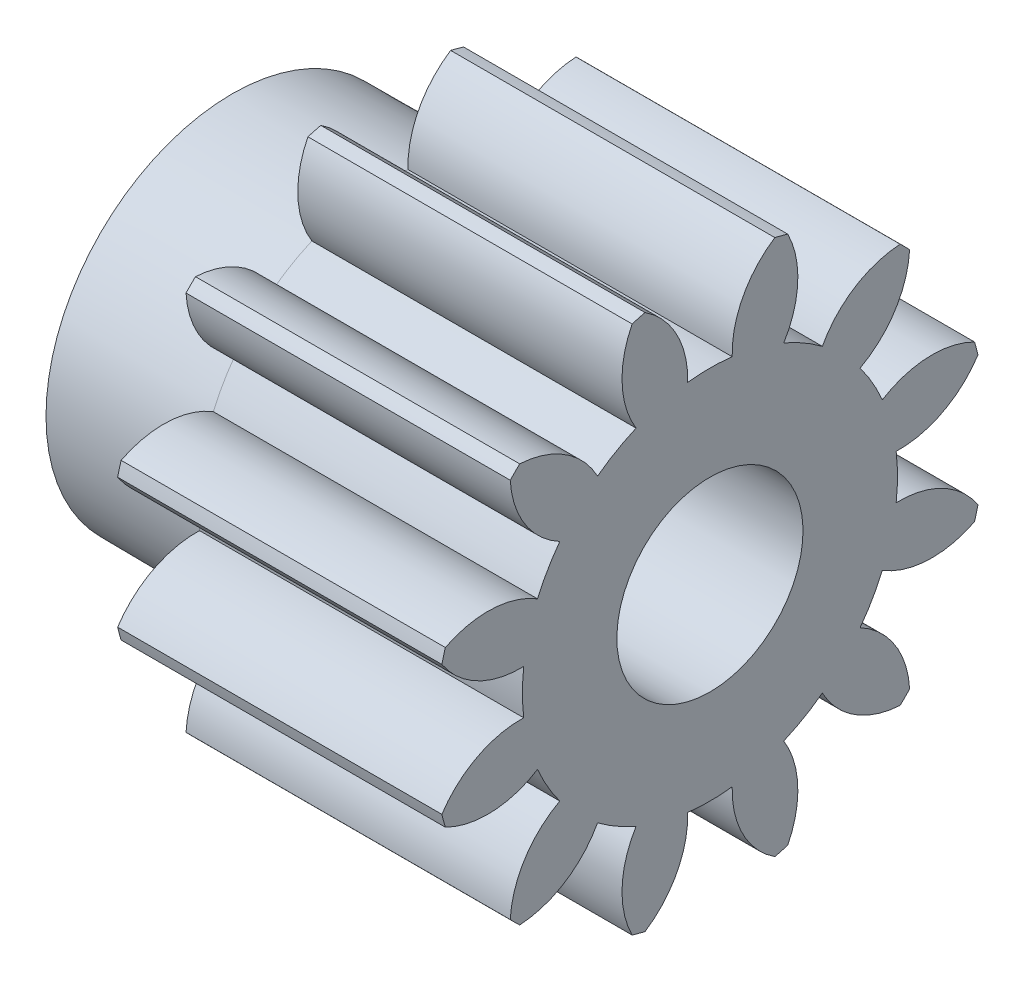
SolidWorks part; units mm, degrees
ref_plane "Plane1" through (0, 0, 0) normal (0, 0, 1) x (1, 0, 0)
ref_plane "Plane2" through (0, 0, 0) normal (0, 1, 0) x (1, 0, 0)
ref_plane "Plane3" through (0, 0, 0) normal (1, 0, 0) x (0, 0, -1)
sketch "HoldingSke" plane through (0, 0, 0) normal (0, 1, 0) x (1, 0, 0)
  line L0 (0, 0) -> (496.899, -105.6191)
  line L1 (-15, 0) -> (100, 0) construction
  line L2 (0, 0) -> (-2.1039, 2.3779)
  line L3 (0, 0) -> (-11.863, 4.5341)
  line L4 (0, 0) -> (8.4473, 1.7955)
  line L5 (0, 0) -> (-47.5972, -17.7524)
  line L6 (0, 0) -> (-10.5278, -7.1032)
  line L7 (-2.1039, 2.3779) -> (8.8308, 51.9871)
  line L8 (-76.2, 54.61) -> (-69.596, 54.61)
  line L9 (-71.009, 38.7566) -> (-53.1078, 45.2721)
  line L10 (-76.2, 71.12) -> (104.1128, 71.12)
  line L11 (0, 0) -> (-12.7, 0)
  line L12 (-76.2, 101.6) -> (-76.1492, 101.6)
  line L13 (24.9733, 27.94) -> (52.9518, 28.4284)
  line L14 (24.9733, 27.94) -> (25.0241, 27.9398)
  line L15 (24.9733, 27.94) -> (100.4021, 29.52)
  circle A0 centre (0, 0) radius 3.175
  circle A1 centre (0, 0) radius 6.0452
  circle A2 centre (0, 0) radius 38.1
  circle A3 centre (0, 0) radius 3.175
  dimension "Num_teeth" = 12
  dimension "H" = 19.05
  dimension "Pitch_radius" = 180.3128
  dimension "Width" = 12.7
  dimension "Thickness" = 12.7
sketch "BasProSke" plane through (0, 0, 0) normal (0, 1, 0) x (1, 0, 0)
  line L0 (-10, 0) -> (60, 0) construction
  line L1 (0, 0) -> (0, 8.89)
  line L2 (0, 0) -> (12.7, 0)
  line L3 (12.7, 0) -> (12.7, 8.89)
  line L4 (12.7, 8.89) -> (0, 8.89)
  dimension "Thickness" = 12.7
  dimension "Diameter" = 17.78
revolve "Base-Revolve" add sketch "BasProSke" angle 360 about L0
sketch "TooCutSke" plane through (0, 0, 0) normal (1, 0, 0) x (0, 0, -1)
  line L1 (0, 0) -> (0, 107) construction
  line L2 (0, 0) -> (-1.0834, 7.5426) construction
  line L3 (0, 0) -> (-3.9164, 14.6164) construction
  line L4 (-1.0834, 7.5426) -> (-1.9582, 7.3082) construction
  arc A0 (0.7171, 6.0025) -> (-0.7171, 6.0025) centre (0, 0) ccw
  arc A1 (2.1216, 8.6593) -> (-2.1216, 8.6593) centre (0, 0) ccw
  circle A2 centre (0, 0) radius 7.62 construction
  circle A3 centre (0, 0) radius 7.1605 construction
  arc A4 (-0.7171, 6.0025) -> (-2.1216, 8.6593) centre (-3.7638, 6.0915) ccw
  arc A5 (2.1216, 8.6593) -> (0.7171, 6.0025) centre (3.7638, 6.0915) ccw
extrude "ToothCut" cut sketch "TooCutSke" along normal through all
fillet "Breaks" [suppressed] radius 0.0254 tangent propagation no
fillet "RootFillets" [suppressed] radius 0.3048
pattern_circular "TeethCuts" count 12 every 30 about axis through (-10, 0, 0) along (1, 0, 0) of "ToothCut", "RootFillets", "Breaks"
sketch "HubNeaOneSke" plane through (0, 0, 0) normal (-1, 0, 0) x (0, 0, 1)
  circle A0 centre (0, 0) radius 6.0452
  dimension "Diameter" = 12.0904
extrude "HubNearOne" [suppressed] add sketch "HubNeaOneSke" along normal blind 38.1001
sketch "HubNeaBotSke" plane through (0, 0, 0) normal (-1, 0, 0) x (0, 0, 1)
  circle A0 centre (0, 0) radius 6.0452
  dimension "Diameter" = 12.0904
extrude "HubNearBoth" [suppressed] add sketch "HubNeaBotSke" along normal blind 19.05
ref_plane "FarPln" through (12.7, 0, 0) normal (1, 0, 0) x (0, 0, -1)
sketch "HubFarSke" plane through (12.7, 0, 0) normal (1, 0, 0) x (0, 0, -1)
  circle A0 centre (0, 0) radius 6.0452
  dimension "Diameter" = 12.0904
extrude "HubFar" [suppressed] add sketch "HubFarSke" along normal blind 19.05
sketch "BorSke" plane through (0, 0, 0) normal (1, 0, 0) x (0, 0, -1)
  circle A0 centre (0, 0) radius 3
  dimension "D1" = 6
extrude "Bore" cut sketch "BorSke" along normal mid plane 101.6001
sketch "KeySke" plane through (0, 0, 0) normal (1, 0, 0) x (0, 0, -1)
  line L0 (-0.127, 0) -> (-0.127, 3.429)
  line L1 (-0.127, 3.429) -> (0.127, 3.429)
  line L2 (0.127, 3.429) -> (0.127, 0)
  line L3 (0, 0) -> (0, 34) construction
  line L4 (-0.127, 0) -> (0.127, 0)
  dimension "Width" = 0.254
extrude "Keyway" [suppressed] cut sketch "KeySke" along normal mid plane 101.6001
pattern_circular "Keyway2" [suppressed] count 2 every 90 about axis through (-10, 0, 0) along (1, 0, 0) reverse direction yes
sketch "Sketch1" plane through (0, 0, 0) normal (0, 0, 1) x (1, 0, 0)
  line L0 (0, 0) -> (-2.5422, 0) construction
  line L1 (0, -4) -> (-4.95, -4)
  line L2 (-4.95, -4) -> (-4.95, -6)
  line L3 (-4.95, -6) -> (0, -6.0452)
  line L4 (0, -6.0452) -> (0, -4)
  dimension "D1" = 2
  dimension "D2" = 4
  dimension "D3" = 4.95
revolve "Revolve1" add sketch "Sketch1" angle 360 about L0
sketch "Sketch2" plane through (0, 0, 0) normal (0, 0, 1) x (1, 0, 0)
  line L0 (12.7, -8.6403) -> (0, -8.6403) construction
  line L1 (12.7, 8.6403) -> (10.45, 8.6403)
  line L2 (12.7, 8.6403) -> (12.7, -8.6403)
  line L3 (12.7, -8.6403) -> (10.45, -8.6403)
  line L4 (10.45, 8.6403) -> (10.45, -8.6403)
  dimension "D1" = 2.25
extrude "Cut-Extrude1" cut sketch "Sketch2" against normal through all both and the other way through all
equation "' \"Pitch@HoldingSke\" = 4"
equation "' \"Num_teeth@HoldingSke\" = 12"
equation "' \"Ap@HoldingSke\" =  20"
equation "' \"Ap@HoldingSke\" = 20"
equation "' \"Width@HoldingSke\" = 0.5"
equation "' \"Hub_dia@HoldingSke\"= 1"
equation "' \"Hub_dia@HoldingSke\" = 1"
equation "' \"Overall_len@HoldingSke\" = 1.0"
equation "' \"Bore@HoldingSke\" = 0.75"
equation "' \"T_dim@HoldingSke\" = 0.85"
equation "' \"Width@KeySke\" = 0.25"
equation "' \"Show_teeth@HoldingSke\" = 13"
equation "' \"Backlash@HoldingSke\" = 0.009"
equation "' \"Addendum_fac@HoldingSke\" = 1.0"
equation "' \"Dedendum_fac@HoldingSke\" = 1.25"
equation "' \"Dedendum_add@HoldingSke\" = 0.00005"
equation "' \"Clearance_fac@HoldingSke\" = 0.25"
equation "' \"Pitch@HoldingSke\" = 0.5"
equation "' \"Num_teeth@HoldingSke\" = 23"
equation "' \"Show_teeth@HoldingSke\" = 23"
equation "' \"Backlash@HoldingSke\" = 0.0375"
equation "\"Overcut_dia@TooCutSke\" = (\"Num_teeth@HoldingSke\" + 2 * \"Addendum_fac@HoldingSke\") / \"Pitch@HoldingSke\" + 0.002"
equation "\"Pitch_dia@TooCutSke\" = \"Num_teeth@HoldingSke\" / \"Pitch@HoldingSke\""
equation "\"Base_dia@TooCutSke\" = \"Num_teeth@HoldingSke\" / \"Pitch@HoldingSke\" * cos((\"Ap@HoldingSke\"  * 3.14159265 / 180))"
equation "\"Root_dia@TooCutSke\" = (\"Num_teeth@HoldingSke\" + 2) / \"Pitch@HoldingSke\" - 2 * (\"Addendum_fac@HoldingSke\" + \"Dedendum_fac@HoldingSke\") / \"Pitch@HoldingSke\" - \"Dedendum_add@HoldingSke\" * 2"
equation "\"Half_ang@TooCutSke\" = 180 / \"Num_teeth@HoldingSke\""
equation "\"Half_CT@TooCutSke\" = \"Num_teeth@HoldingSke\" / \"Pitch@HoldingSke\" * sin((3.14159265 / 2 / \"Num_teeth@HoldingSke\")) / 2 - 7 * \"Backlash@HoldingSke\" / 4"
equation "\"Flank_rad@TooCutSke\" = \"Num_teeth@HoldingSke\" / \"Pitch@HoldingSke\" / 5"
equation "\"Radius@RootFillets\" = \"Clearance_fac@HoldingSke\" / \"Pitch@HoldingSke\" + \"Dedendum_add@HoldingSke\""
equation "\"Break_rad@Breaks\" = 0.02 / \"Pitch@HoldingSke\""
equation "\"Thickness@HoldingSke\" = \"Width@HoldingSke\""
equation "\"OAL@HoldingSke\" = \"Thickness@HoldingSke\""
equation "\"MHD@HoldingSke\" = (\"Num_teeth@HoldingSke\" + 2) / \"Pitch@HoldingSke\" - 2 * (\"Addendum_fac@HoldingSke\" + \"Dedendum_fac@HoldingSke\")  / \"Pitch@HoldingSke\" - \"Dedendum_add@HoldingSke\" * 2"
equation "\"MBD@HoldingSke\" = (\"Num_teeth@HoldingSke\" + 2) / \"Pitch@HoldingSke\" - 2 * (\"Addendum_fac@HoldingSke\" + \"Dedendum_fac@HoldingSke\")  / \"Pitch@HoldingSke\" - \"Dedendum_add@HoldingSke\" * 2 - 0.002"
equation "\"MHD@HoldingSke\" = ((sgn( \"MHD@HoldingSke\" - \"Hub_dia@HoldingSke\" )-1)*( \"MHD@HoldingSke\" - \"Hub_dia@HoldingSke\" ))/-2+ \"Hub_dia@HoldingSke\""
equation "\"MBD@HoldingSke\" = ((sgn( \"MBD@HoldingSke\" - \"Bore@HoldingSke\" )-1)*( \"MBD@HoldingSke\" - \"Bore@HoldingSke\" ))/-2+ \"Bore@HoldingSke\""
equation "\"OAL@HoldingSke\" = ((sgn( \"OAL@HoldingSke\" - \"Overall_len@HoldingSke\" )+1)*( \"OAL@HoldingSke\" - \"Overall_len@HoldingSke\" ))/2 + \"Overall_len@HoldingSke\" + 0.000002"
equation "\"Num_teeth@TeethCuts\" = int( \"Show_teeth@HoldingSke\" ) + 1"
equation "\"Num_teeth@TeethCuts\" = ((sgn( \"Num_teeth@TeethCuts\" - \"Num_teeth@HoldingSke\" )-1)*( \"Num_teeth@TeethCuts\" - \"Num_teeth@HoldingSke\" ))/-2+ \"Num_teeth@HoldingSke\""
equation "\"Num_teeth@TeethCuts\" = ((sgn( \"Num_teeth@TeethCuts\" - 2.0)+1)*( \"Num_teeth@TeethCuts\" - 2.0))/2 +2.0"
equation "\"Angle@TeethCuts\" = 360.0 / \"Num_teeth@HoldingSke\""
equation "\"Diameter@BasProSke\" = (\"Num_teeth@HoldingSke\" + 2 * \"Addendum_fac@HoldingSke\") / \"Pitch@HoldingSke\""
equation "\"Thickness@BasProSke\"  = \"Thickness@HoldingSke\""
equation "' \"Fillet_rad@BasProSke\" =  \"Thickness@HoldingSke\" * 0.05"
equation "' \"Fillet_rad@BasProSke\" = \"Thickness@HoldingSke\" * 0.05"
equation "\"MHD@HoldingSke\" = ((sgn( \"MHD@HoldingSke\" - \"Root_dia@TooCutSke\" )-1)*( \"MHD@HoldingSke\" - \"Root_dia@TooCutSke\" ))/-2+ \"Root_dia@TooCutSke\""
equation "\"Diameter@HubNeaOneSke\" = \"MHD@HoldingSke\""
equation "\"Length@HubNearOne\" = \"OAL@HoldingSke\" - \"Thickness@BasProSke\""
equation "\"Diameter@HubNeaBotSke\" = \"MHD@HoldingSke\""
equation "\"Length@HubNearBoth\" = ( \"OAL@HoldingSke\" - \"Thickness@BasProSke\" ) / 2.0"
equation "\"Thickness@FarPln\" = \"Thickness@BasProSke\""
equation "\"Diameter@HubFarSke\" = \"MHD@HoldingSke\""
equation "\"Length@HubFar\" = ( \"OAL@HoldingSke\" - \"Thickness@BasProSke\" ) / 2.0"
equation "\"D1@Bore\" = \"OAL@HoldingSke\" * 2.0"
equation "\"D1@Keyway\" = \"OAL@HoldingSke\" * 2.0"
equation "\"Offset@KeySke\" = \"T_dim@HoldingSke\" - \"MBD@HoldingSke\" / 2.0"
